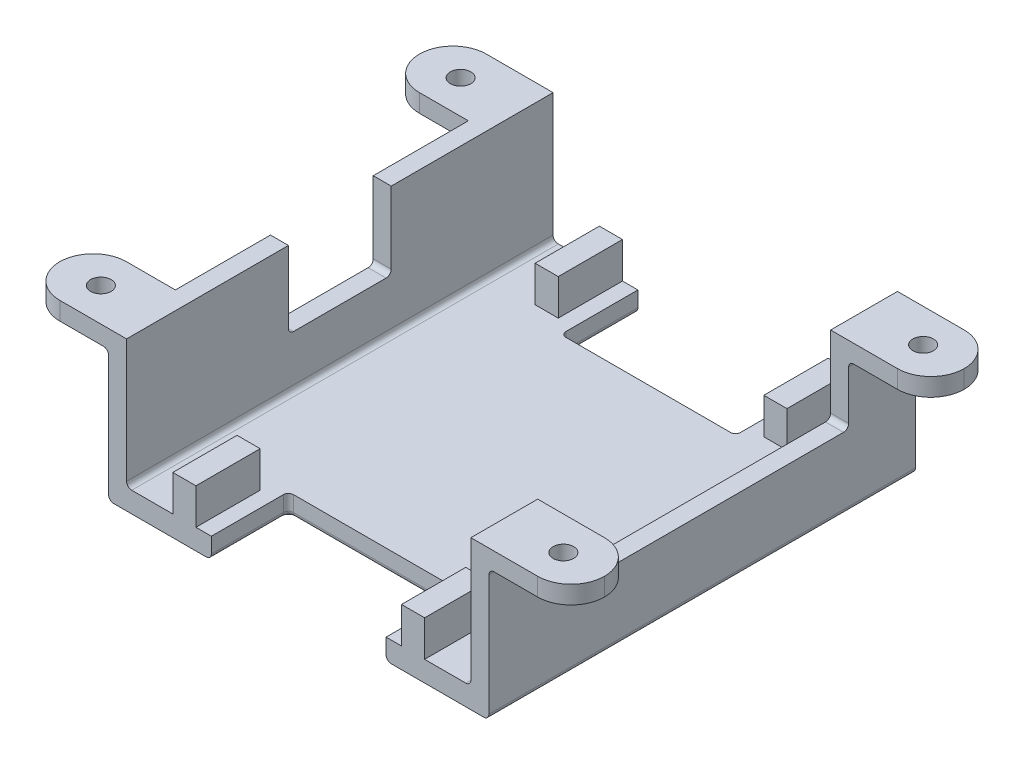
SolidWorks part; units mm, degrees
ref_plane "Front Plane" through (0, 0, 0) normal (0, 0, 1) x (1, 0, 0)
ref_plane "Top Plane" through (0, 0, 0) normal (0, 1, 0) x (1, 0, 0)
ref_plane "Right Plane" through (0, 0, 0) normal (1, 0, 0) x (0, 0, -1)
sketch "Sketch1" plane through (0, 0, 0) normal (0, 1, 0) x (1, 0, 0)
  line L1 (-37, 26.5) -> (37, 26.5)
  line L2 (-37, 26.5) -> (-37, -26.5)
  line L3 (-37, -26.5) -> (37, -26.5)
  line L4 (37, 26.5) -> (37, -26.5)
  line L5 (-37, 26.5) -> (37, -26.5) construction
  line L6 (-37, -26.5) -> (37, 26.5) construction
  point P0 (0, 0)
  dimension "D1" = 74
  dimension "D2" = 53
extrude "Boss-Extrude1" add sketch "Sketch1" along normal blind 4
sketch "Sketch2" plane through (0, 4, 0) normal (0, 1, 0) x (1, 0, 0)
  line L0 (-37, -26.5) -> (37, -26.5) construction
  line L1 (-37, 26.5) -> (-33.5, 26.5)
  line L2 (-37, 26.5) -> (-37, -26.5)
  line L3 (-37, -26.5) -> (-33.5, -26.5)
  line L4 (-33.5, 26.5) -> (-33.5, -26.5)
  dimension "D1" = 3.5
extrude "Boss-Extrude2" add sketch "Sketch2" along normal blind 25
mirror "Mirror1" about plane through (0, 0, 0) normal (1, 0, 0) of "Boss-Extrude2"
sketch "Sketch3" plane through (-37, 0, 0) normal (-1, 0, 0) x (0, 0, 1)
  line L0 (-26.5, 29) -> (26.5, 29) construction
  line L1 (-10, 29) -> (10, 29)
  line L2 (-10, 29) -> (-10, 14)
  line L3 (-10, 14) -> (10, 14)
  line L4 (10, 29) -> (10, 14)
  line L5 (-26.5, 29) -> (-26.5, 0) construction
  dimension "D1" = 15
  dimension "D2" = 20
  dimension "D3" = 16.5
extrude "Cut-Extrude1" cut sketch "Sketch3" against normal up to next
sketch "Sketch5" plane through (0, 0, -26.5) normal (0, 0, -1) x (-1, 0, 0)
  line L0 (-33.5, 4) -> (33.5, 4) construction
  line L1 (37, 0) -> (17, 0)
  line L2 (37, 0) -> (37, 4)
  line L3 (37, 4) -> (17, 4)
  line L4 (17, 0) -> (17, 4)
  dimension "D1" = 20
extrude "Boss-Extrude4" add sketch "Sketch5" along normal blind 15
mirror "Mirror3" about plane through (0, 0, 0) normal (0, 0, 1) of "Boss-Extrude4"
mirror "Mirror4" about plane through (0, 0, 0) normal (1, 0, 0) of "Mirror3"
sketch "Sketch6" plane through (0, 4, 0) normal (0, 1, 0) x (1, 0, 0)
  line L1 (-37, 41.5) -> (-33.5, 41.5)
  line L2 (-37, 41.5) -> (-37, 26.5)
  line L3 (-37, 26.5) -> (-33.5, 26.5)
  line L4 (-33.5, 41.5) -> (-33.5, 26.5)
extrude "Boss-Extrude5" add sketch "Sketch6" along normal up to surface (25 mm away) up to face at (-35.25, 29, -18.25)
mirror "Mirror5" about plane through (0, 0, 0) normal (0, 0, 1) of "Boss-Extrude5"
mirror "Mirror6" about plane through (0, 0, 0) normal (1, 0, 0) of "Mirror5"
sketch "Sketch7" plane through (0, 4, 0) normal (0, 1, 0) x (1, 0, 0)
  line L0 (-33.5, 41.5) -> (-17, 41.5) construction
  line L1 (-24.5, 41.5) -> (-20, 41.5)
  line L2 (-24.5, 41.5) -> (-24.5, 29)
  line L3 (-24.5, 29) -> (-20, 29)
  line L4 (-20, 41.5) -> (-20, 29)
  line L5 (17, 26.5) -> (-17, 26.5) construction
  dimension "D1" = 4.5
  dimension "D2" = 9
  dimension "D3" = 2.5
extrude "Boss-Extrude6" add sketch "Sketch7" along normal blind 7
mirror "Mirror7" about plane through (0, 0, 0) normal (0, 0, 1) of "Boss-Extrude6"
mirror "Mirror8" about plane through (0, 0, 0) normal (1, 0, 0) of "Mirror7"
sketch "Sketch8" plane through (-37, 0, 0) normal (-1, 0, 0) x (0, 0, 1)
  line L1 (-41.5, 29) -> (-28.5, 29)
  line L2 (-41.5, 29) -> (-41.5, 25.5)
  line L3 (-41.5, 25.5) -> (-28.5, 25.5)
  line L4 (-28.5, 29) -> (-28.5, 25.5)
  dimension "D1" = 3.5
  dimension "D2" = 13
extrude "Boss-Extrude7" add sketch "Sketch8" along normal blind 16
mirror "Mirror9" about plane through (0, 0, 0) normal (0, 0, 1) of "Boss-Extrude7"
mirror "Mirror10" about plane through (0, 0, 0) normal (1, 0, 0) of "Mirror9"
sketch "Sketch9" plane through (37, 0, 0) normal (1, 0, 0) x (0, 0, -1)
  line L0 (28.5, 14) -> (-28.5, 29) construction
  line L5 (-28.5, 14) -> (28.5, 29) construction
  line L11 (28.5, 14) -> (-28.5, 14)
  line L12 (28.5, 14) -> (28.5, 29)
  line L13 (28.5, 29) -> (-28.5, 29)
  line L14 (-28.5, 14) -> (-28.5, 29)
  line L15 (28.5, 14) -> (-28.5, 29) construction
  line L16 (28.5, 29) -> (-28.5, 14) construction
  point P5 (0, 21.5)
  dimension "D1" = 57
  dimension "D2" = 15
extrude "Cut-Extrude2" cut sketch "Sketch9" against normal up to next
sketch "Sketch11" plane through (0, 25.5, 0) normal (0, -1, 0) x (1, 0, 0)
  line L0 (-53, 35) -> (-37, 35) construction
  line L1 (-53, 41.5) -> (-53, 28.5) construction
  line L2 (-37, 41.5) -> (-37, 28.5) construction
  line L3 (-53, -35) -> (-37, -35) construction
  line L4 (-53, -41.5) -> (-53, -28.5) construction
  line L5 (-37, -41.5) -> (-37, -28.5) construction
  line L6 (37, 35) -> (53, 35) construction
  line L7 (37, 41.5) -> (37, 28.5) construction
  line L8 (53, 41.5) -> (53, 28.5) construction
  line L9 (53, -35) -> (37, -35) construction
  line L10 (53, -41.5) -> (53, -28.5) construction
  line L11 (37, 41.5) -> (37, -41.5) construction
  point P24 (45, -35)
  point P25 (45, 35)
  point P26 (-45, 35)
  point P27 (-45, -35)
hole_wizard "Ø4.0mm Clearance Dowel Hole1" positions "Sketch13" profile "Sketch14" hole size "Ø4.0" standard "ANSI Metric" end condition through all
sketch "Sketch13" plane through (0, 25.5, 0) normal (0, -1, 0) x (-1, 0, 0)
  point P0 (-45, 35)
  point P3 (-45, -35)
  point P6 (45, 35)
  point P9 (45, -35)
sketch "Sketch14" plane through (45, 25.5, -35) normal (1, 0, 0) x (0, 0, -1)
  line L0 (0, 0) -> (0, 3.5)
  line L1 (0, 3.5) -> (2, 3.5)
  line L2 (2, 3.5) -> (2, 0)
  line L5 (2, 0) -> (0, 0)
  line L11 (0, -6.35) -> (0, 107.95) construction
  dimension "Thru Hole Dia." = 4
  dimension "Thru Hole Depth" = 3.5
sketch "Sketch15" plane through (0, 0, 28.5) normal (0, 0, -1) x (-1, 0, 0)
  line L1 (53, 29) -> (37, 29)
  line L2 (53, 29) -> (53, 25.5)
  line L3 (53, 25.5) -> (37, 25.5)
  line L4 (37, 29) -> (37, 25.5)
fillet "Fillet1" radius 6.5 8 edges at (53, 27.25, -28.5) (53, 27.25, -41.5) (53, 27.25, 28.5) (53, 27.25, 41.5) (-53, 27.25, -41.5) (-53, 27.25, -28.5) (-53, 27.25, 28.5) (-53, 27.25, 41.5)
fillet "Fillet2" radius 1 14 edges at (-33.5, 4, 0) (17, 2, -26.5) (-17, 2, -26.5) (-17, 2, 26.5) (17, 2, 26.5) (-37, 25.5, -35) (-37, 25.5, 35) (-35.25, 14, -10) (-35.25, 14, 10) (35.25, 14, 28.5) (35.25, 14, -28.5) (33.5, 4, 0) (37, 25.5, -35) (37, 25.5, 35)
fillet "Fillet3" radius 1 12 edges at (-17, 0, -34.5) (-16.7071, 0, -26.7929) (0, 0, -26.5) (16.7071, 0, -26.7929) (-17, 0, 34.5) (-16.7071, 0, 26.7929) (0, 0, 26.5) (16.7071, 0, 26.7929) (17, 0, -34.5) (17, 0, 34.5) (-37, 0, 0) (37, 0, 0)
